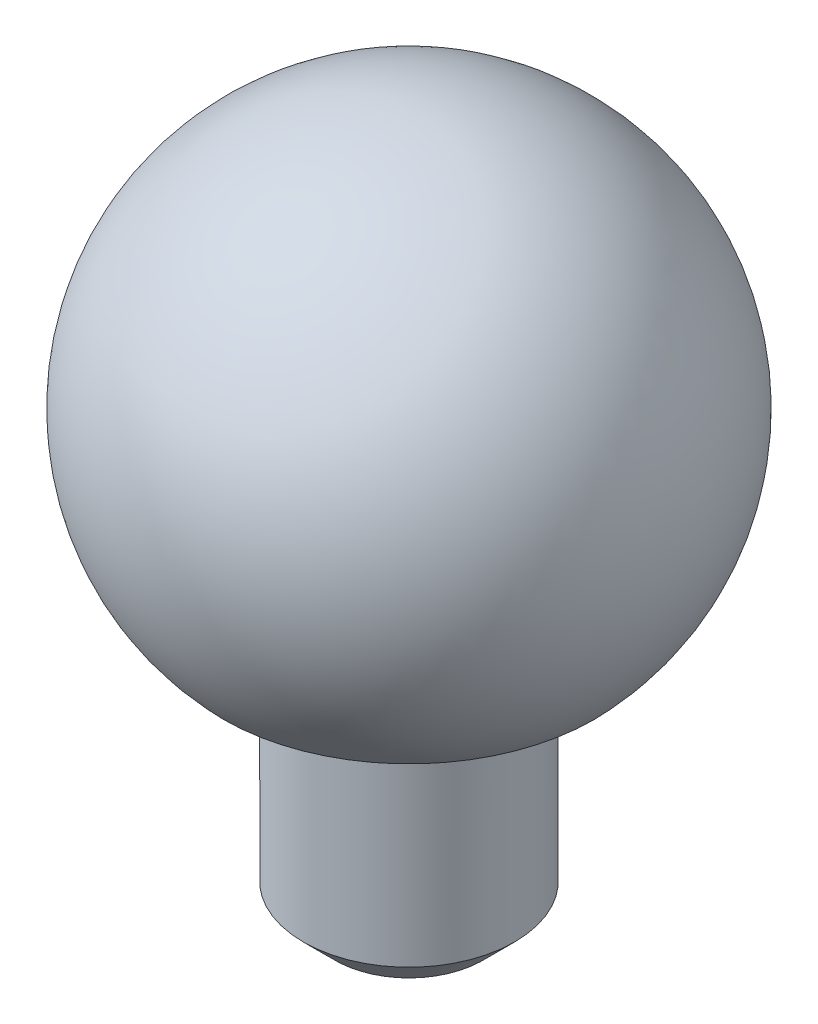
SolidWorks part; units mm, degrees
ref_plane "Ebene vorne" through (0, 0, 0) normal (0, 0, 1) x (1, 0, 0)
ref_plane "Ebene oben" through (0, 0, 0) normal (0, 1, 0) x (1, 0, 0)
ref_plane "Ebene rechts" through (0, 0, 0) normal (1, 0, 0) x (0, 0, -1)
sketch "Skizze1" plane through (0, 0, 0) normal (1, 0, 0) x (0, 0, -1)
  line L0 (0, 21.1126) -> (0, -19.4987) construction
  line L1 (-21.4129, 0) -> (22.0134, 0) construction
  line L2 (0, 4.85) -> (0, -3.35)
  line L3 (0, -3.35) -> (3.5071, -3.35)
  arc A0 (0, 4.85) -> (3.5071, -3.35) centre (0, 0) cw
  dimension "D1" = 4.85
  dimension "D2" = 8.2
revolve "Rotation1" add sketch "Skizze1" angle 360 about L0 region at (0, 0.4316, -2.1359)
ref_axis "Achse1" through (0, -12.0116, 0) along (0, 1, 0)
sketch "Skizze2" plane through (0, -3.35, 0) normal (0, -1, 0) x (1, 0, 0)
  circle A0 centre (0, 0) radius 2
  dimension "D1" = 4
extrude "Aufsatz-Linear austragen1" add sketch "Skizze2" along normal blind 5
chamfer "Fase1" distance 0.6 angle 45 1 edges at (0, -8.35, -2)
